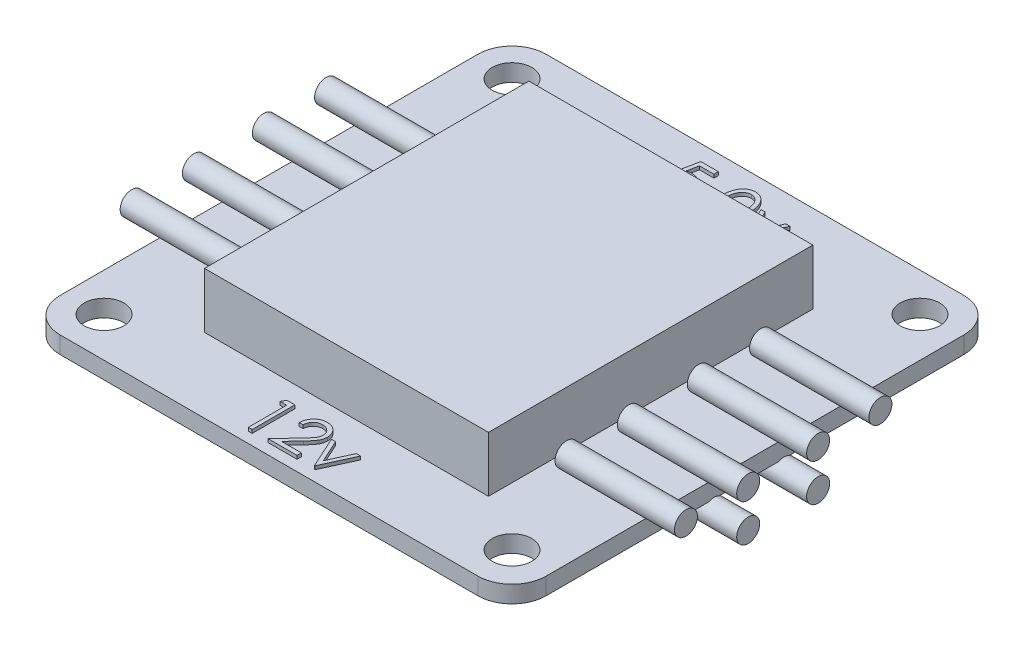
SolidWorks part; units mm, degrees
material "A-Glass Fiber"
ref_plane "Front Plane" through (0, 0, 0) normal (0, 0, 1) x (1, 0, 0)
ref_plane "Top Plane" through (0, 0, 0) normal (0, 1, 0) x (1, 0, 0)
ref_plane "Right Plane" through (0, 0, 0) normal (1, 0, 0) x (0, 0, -1)
sketch "Sketch1" plane through (0, 0, 0) normal (0, 1, 0) x (1, 0, 0)
  line L1 (-18.0975, -18.0975) -> (18.0975, -18.0975)
  line L2 (-18.0975, -18.0975) -> (-18.0975, 18.0975)
  line L3 (-18.0975, 18.0975) -> (18.0975, 18.0975)
  line L4 (18.0975, -18.0975) -> (18.0975, 18.0975)
  line L5 (-18.0975, -18.0975) -> (18.0975, 18.0975) construction
  line L6 (-18.0975, 18.0975) -> (18.0975, -18.0975) construction
  point P0 (0, 0)
  dimension "D1" = 36.195
extrude "Boss-Extrude1" add sketch "Sketch1" along normal blind 1.27
sketch "Sketch2" plane through (0, 1.27, 0) normal (0, 1, 0) x (1, 0, 0)
  line L0 (18.0975, -18.0975) -> (18.0975, 18.0975) construction
  line L1 (-10.3378, -12.5603) -> (10.8077, -12.5603)
  line L2 (-10.3378, -12.5603) -> (-10.3378, 11.5951)
  line L3 (-10.3378, 11.5951) -> (10.8077, 11.5951)
  line L4 (10.8077, -12.5603) -> (10.8077, 11.5951)
  line L5 (-10.3378, -12.5603) -> (10.8077, 11.5951) construction
  line L6 (-10.3378, 11.5951) -> (10.8077, -12.5603) construction
  line L7 (18.0975, 18.0975) -> (-18.0975, 18.0975) construction
  point P0 (0.2349, -0.4826)
  dimension "D1" = 21.1455
  dimension "D2" = 24.1554
  dimension "D3" = 7.2898
  dimension "D4" = 6.5024
extrude "Boss-Extrude2" add sketch "Sketch2" along normal blind 4.1275
sketch "Sketch3" plane through (0, 1.27, 0) normal (0, 1, 0) x (1, 0, 0)
  text T0 "5.0v"
  text T1 "12v"
extrude "Boss-Extrude3" add sketch "Sketch3" along normal blind 0.254
hole_wizard "#4 Clearance Hole1" positions "Sketch5" profile "Sketch4" hole size "#4" standard "ANSI Inch" end condition up to next
sketch "Sketch5" plane through (0, 1.27, 0) normal (0, 1, 0) x (1, 0, 0)
  line L0 (-18.0975, 18.0975) -> (-18.0975, -18.0975) construction
  line L1 (18.0975, 18.0975) -> (-18.0975, 18.0975) construction
  point P0 (15.1384, 15.24)
  point P2 (-15.24, 15.24)
  point P4 (15.1384, -15.1384)
  point P6 (-15.24, -15.1384)
  dimension "D1" = 30.3784
  dimension "D2" = 2.8575
  dimension "D3" = 2.8575
  dimension "D4" = 30.3784
sketch "Sketch4" plane through (15.1384, 1.27, -15.24) normal (1, 0, 0) x (0, 0, 1)
  line L0 (0, 0) -> (0, 1.27)
  line L1 (0, 1.27) -> (1.4732, 1.27)
  line L2 (1.4732, 1.27) -> (1.4732, 0)
  line L5 (1.4732, 0) -> (0, 0)
  line L11 (0, -6.35) -> (0, 107.95) construction
  dimension "Thru Hole Dia." = 2.9464
  dimension "Thru Hole Depth" = 1.27
fillet "Fillet1" radius 2.54 4 edges at (-18.0975, 0.635, 18.0975) (18.0975, 0.635, 18.0975) (18.0975, 0.635, -18.0975) (-18.0975, 0.635, -18.0975)
sketch "Sketch6" plane through (-18.0975, 0, 0) normal (-1, 0, 0) x (0, 0, 1)
  line L1 (-15.5575, 1.27) -> (15.5575, 1.27) construction
  circle A0 centre (-6.7945, 2.032) radius 0.8573
  circle A1 centre (-2.159, 2.032) radius 0.8573
  circle A2 centre (3.048, 2.032) radius 0.8573
  circle A3 centre (7.6835, 2.032) radius 0.8573
  line M3 (15.5575, 1.27) -> (-15.5575, 1.27)
  dimension "D5" = 1.7145
  dimension "D1" = 4.6355
  dimension "D2" = 4.6355
  dimension "D3" = 14.478
  dimension "D4" = 10.414
  dimension "D6" = 0.762
extrude "Boss-Extrude4" add sketch "Sketch6" along normal blind 2.54 and the other way blind 6.35 separate body contours A0 M3 | A0 M3 | A1 M3 | A1 | A2 | A3 region at (-18.0975, 2.0499, -6.7945) region at (-18.0975, 2.0499, -2.159) region at (-18.0975, 1.2317, -6.7945)
sketch "Sketch7" plane through (18.0975, 0, 0) normal (1, 0, 0) x (0, 0, -1)
  line L0 (-15.5575, 0.635) -> (15.5575, 0.635) construction
  line L1 (-15.5575, 1.27) -> (-15.5575, 0) construction
  line L2 (15.5575, 0) -> (15.5575, 1.27) construction
  circle A0 centre (-7.6835, 2.032) radius 0.8573 construction
  circle A1 centre (-3.048, 2.032) radius 0.8573 construction
  circle A2 centre (2.159, 2.032) radius 0.8573 construction
  circle A3 centre (6.7945, 2.032) radius 0.8573 construction
  circle A4 centre (-7.6835, 2.032) radius 0.8573
  circle A5 centre (-3.048, 2.032) radius 0.8573
  circle A6 centre (2.159, 2.032) radius 0.8573
  circle A7 centre (6.7945, 2.032) radius 0.8573
  circle A8 centre (2.159, -0.762) radius 0.8573
  circle A9 centre (-3.048, -0.762) radius 0.8573
extrude "Boss-Extrude5" add sketch "Sketch7" along normal blind 2.54 and the other way blind 6.35
combine bodies "Combine1" operation type add bodies to combine 109 104 110 111 112 114 117 116 115 119 118
